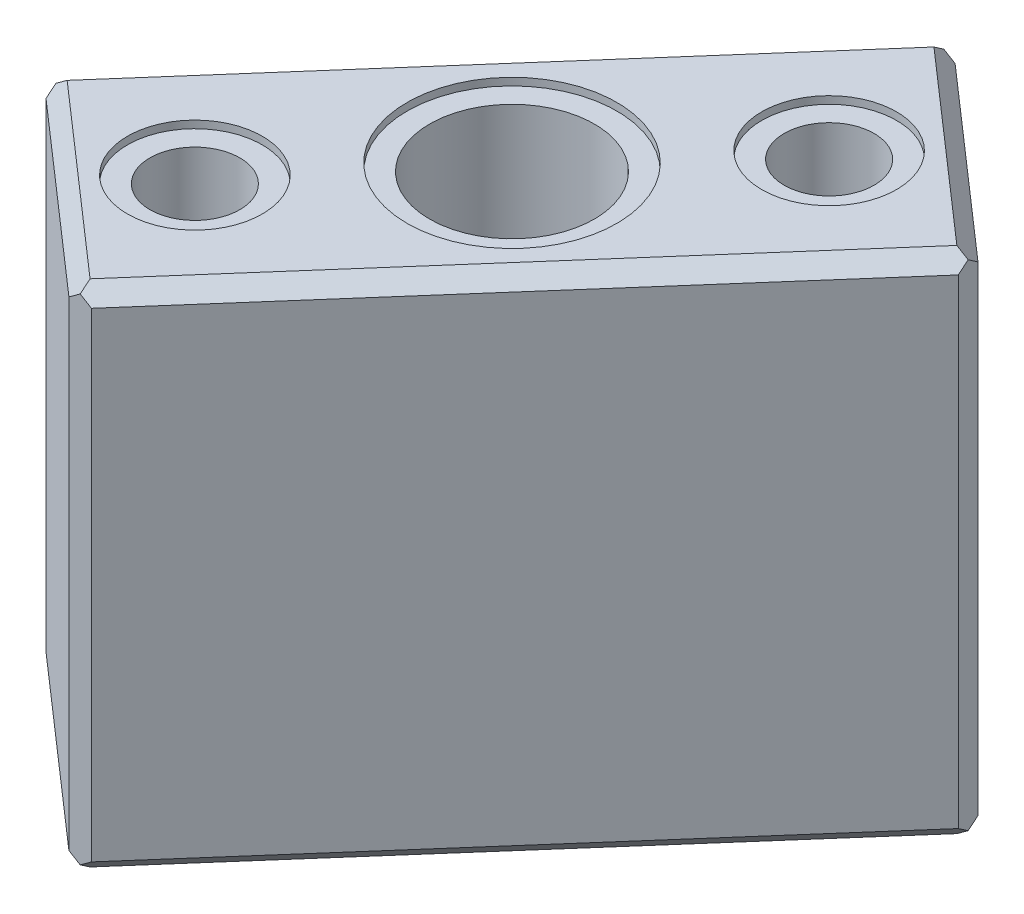
SolidWorks part; units mm, degrees
material "ABS"
ref_plane "Front Plane" through (0, 0, 0) normal (0, 0, 1) x (1, 0, 0)
ref_plane "Top Plane" through (0, 0, 0) normal (0, 1, 0) x (1, 0, 0)
ref_plane "Right Plane" through (0, 0, 0) normal (1, 0, 0) x (0, 0, -1)
sketch "Sketch1" plane through (0, 0, 0) normal (0, 1, 0) x (1, 0, 0)
  line L0 (-119.3719, -118.8922) -> (-105.214, -102.7118)
  line L5 (-105.214, -102.7118) -> (-112.0842, -96.7004)
  line L6 (-112.0842, -96.7004) -> (-126.242, -112.8808)
  line L7 (-126.242, -112.8808) -> (-119.3719, -118.8922)
  line L9 (-119.3719, -118.8922) -> (-112.0842, -96.7004) construction
  line L10 (-122.807, -115.8865) -> (-108.6491, -99.7061) construction
  line L13 (-126.242, -112.8808) -> (-126.4853, -112.8232)
  circle A0 centre (-115.728, -107.7963) radius 2.75 construction
  circle A1 centre (-115.728, -107.7963) radius 2.75 construction
  circle A2 centre (-110.7892, -102.152) radius 1.5 construction
  circle A3 centre (-120.6668, -113.4406) radius 1.5 construction
  circle A4 centre (-110.7892, -102.152) radius 1.5 construction
  circle A5 centre (-120.6668, -113.4406) radius 1.5 construction
  spline S1 degree 2 poles (-124.9067, -110.0456) (-125.3239, -110.5666) (-125.5434, -110.876) (-125.8852, -111.3577) (-126.1057, -111.7974) (-126.3696, -112.3239) (-126.4896, -112.8416) (-126.6235, -113.4192) (-126.5753, -113.9642) (-126.5255, -114.5274) (-126.3683, -115.0757) (-126.2115, -115.6227) (-125.9548, -116.1279) (-125.6986, -116.6322) (-125.3486, -117.0823) (-124.9993, -117.5315) (-124.5728, -117.9047) (-124.1472, -118.2772) (-123.6547, -118.5644) (-123.1632, -118.8511) (-122.6284, -119.0386) (-122.0946, -119.2257) (-121.5306, -119.3088) (-120.9675, -119.3917) (-120.4015, -119.3664) (-119.8557, -119.342) (-119.3002, -119.1324) (-118.8039, -118.9452) (-118.3162, -118.6132) (-117.9104, -118.3371) (-117.4775, -117.9337) (-117.2005, -117.6755) (-116.739, -117.1923) knots 0 0 0 0.0625 0.0625 0.125 0.125 0.1875 0.1875 0.25 0.25 0.3125 0.3125 0.375 0.375 0.4375 0.4375 0.5 0.5 0.5625 0.5625 0.625 0.625 0.6875 0.6875 0.75 0.75 0.8125 0.8125 0.875 0.875 0.9375 0.9375 1 1 1 construction
  point P10 (-115.728, -107.7963)
  dimension "D1" = 0.25
  dimension "D2" = 21.5
extrude "Boss-Extrude1" add sketch "Sketch1" against normal offset from surface (17 mm away) 1.5 from surface at -1.5 contours L0 L5 L6 L7
chamfer "Chamfer1" distance 0.5 angle 45 4 edges at (-119.3719, -10, 118.8922) (-126.242, -10, 112.8808) (-112.0842, -10, 96.7004) (-105.214, -10, 102.7118)
chamfer "Chamfer2" distance 0.5 angle 45 8 edges at (-108.6491, -18.5, 99.7061) (-119.1631, -18.5, 104.7906) (-122.807, -18.5, 115.8865) (-112.293, -18.5, 110.802) (-108.6491, -1.5, 99.7061) (-119.1631, -1.5, 104.7906) (-122.807, -1.5, 115.8865) (-112.293, -1.5, 110.802)
surface "Surface-Offset1" parameters "D1"=0
sketch "Sketch3" plane through (0, -1.5, 0) normal (0, 1, 0) x (1, 0, 0)
  circle A2 centre (-110.7892, -102.152) radius 2.25
  circle A3 centre (-110.7892, -102.152) radius 2.25
  circle A5 centre (-115.728, -107.7963) radius 3.5
  circle A6 centre (-115.728, -107.7963) radius 3.5
  circle A8 centre (-120.6668, -113.4406) radius 2.25
  circle A9 centre (-120.6668, -113.4406) radius 2.25
  dimension "D1" = 1
  dimension "D2" = 1
  dimension "D3" = 1
extrude "Cut-Extrude1" cut sketch "Sketch3" against normal blind 0.25
sketch "Sketch4" plane through (0, -1.5, 0) normal (0, 1, 0) x (1, 0, 0)
  circle A2 centre (-110.7892, -102.152) radius 1.5
  circle A3 centre (-110.7892, -102.152) radius 1.5
  circle A5 centre (-115.728, -107.7963) radius 2.75
  circle A6 centre (-115.728, -107.7963) radius 2.75
  circle A8 centre (-120.6668, -113.4406) radius 1.5
  circle A9 centre (-120.6668, -113.4406) radius 1.5
  dimension "D2" = 0.25
  dimension "D3" = 0.25
extrude "Cut-Extrude2" cut sketch "Sketch4" against normal blind 10
equation "\"hTolerance\"= .25"
equation "\"wThick\"= 1.5"
equation "\"wTolerance\"= .5"
equation "\"D3@Sketch4\"=\"hTolerance\""
equation "\"D2@Sketch4\"=\"hTolerance\""
equation "\"D1@Sketch4\"=\"hTolerance\""
